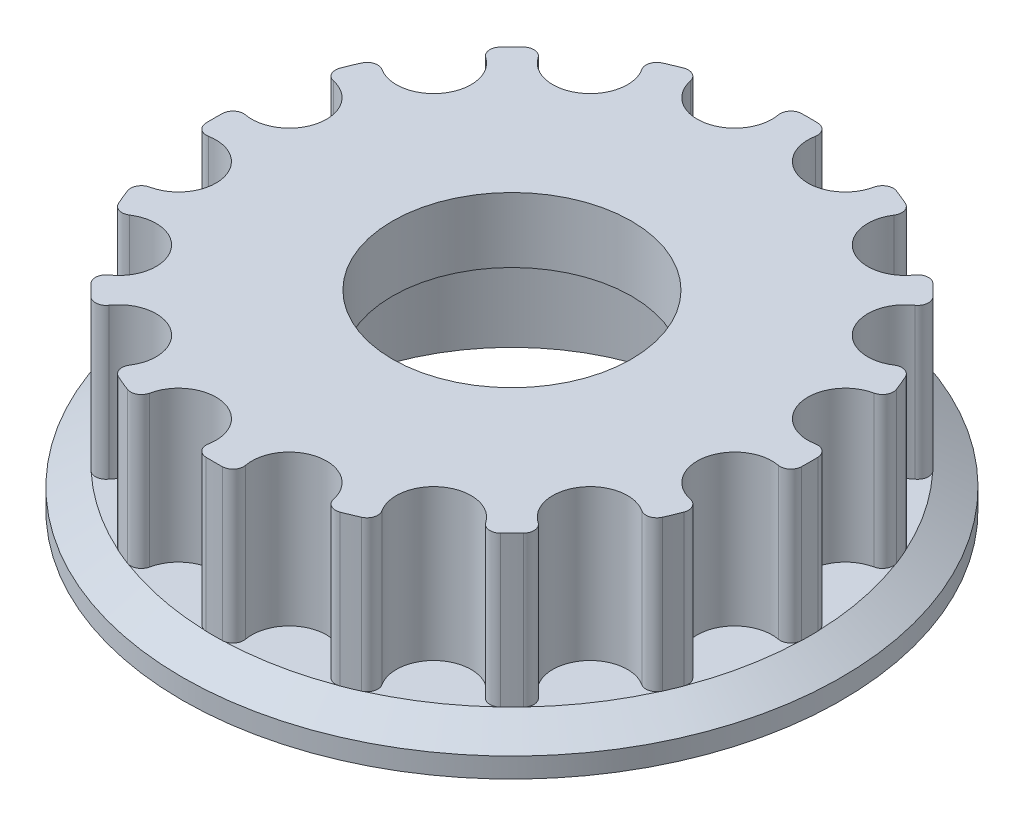
SolidWorks part; units mm, degrees
ref_plane "Front Plane" through (0, 0, 0) normal (0, 0, 1) x (1, 0, 0)
ref_plane "Top Plane" through (0, 0, 0) normal (0, 1, 0) x (1, 0, 0)
ref_plane "Right Plane" through (0, 0, 0) normal (1, 0, 0) x (0, 0, -1)
sketch "Sketch1" plane through (0, 0, 0) normal (0, 1, 0) x (1, 0, 0)
  circle A0 centre (0, 0) radius 12.7324
  dimension "D1" = 25.4648
extrude "Boss-Extrude1" add sketch "Sketch1" along normal blind 6
sketch "Sketch3" plane through (0, 0, 0) normal (0, 1, 0) x (1, 0, 0)
  line L3 (0, 0) -> (0, 11.8624) construction
  line L6 (0, 0) -> (2.484, 12.4877) construction
  line L8 (5.2552, 12.6871) -> (4.5395, 10.9594)
  line L9 (0, 13.7324) -> (0, 11.8624)
  arc A2 (0, 12.7324) -> (4.8725, 11.7632) centre (0, 0) cw construction
  arc A8 (0, 11.8624) -> (0.3276, 11.8579) centre (0, 0) cw
  arc A9 (0.7384, 11.3491) -> (0.3276, 11.8579) centre (0.3157, 11.428) ccw
  arc A12 (0.7384, 11.3491) -> (3.6609, 10.7677) centre (2.203, 11.0754) ccw
  arc A15 (3.6609, 10.7677) -> (4.2352, 11.0806) centre (4.0817, 10.6789) cw
  arc A16 (4.5395, 10.9594) -> (4.2352, 11.0806) centre (0, 0) ccw
  arc A17 (0, 13.7324) -> (5.2552, 12.6871) centre (0, 0) cw
  circle A18 centre (0, 0) radius 12.7324 construction
  dimension "D1" = 0.43
  dimension "D2" = 1.49
  dimension "D4" = 2.93
  dimension "D5" = 5
  dimension "D3" = 0.87
  dimension "D6" = 1
extrude "Cut-Extrude1" cut sketch "Sketch3" along normal up to surface (6 mm away) up to face at (0, 6, 12.7324)
pattern_circular "CirPattern1" count 16 over 360 about axis through (0, 6, 0) along (0, 1, 0) of "Cut-Extrude1"
sketch "Sketch5" plane through (0, 0, 0) normal (0, 0, 1) x (1, 0, 0)
  line L0 (0, 0) -> (0, -1.5875)
  line L1 (0, -1.5875) -> (-13.1279, -1.5875)
  line L2 (-13.1279, -1.5875) -> (-13.1279, -0.7938)
  line L3 (-13.1279, -0.7938) -> (-11.8579, 0)
  line L4 (55, 0) -> (-55, 0) construction
  line L5 (-11.8579, 0) -> (0, 0)
  line L6 (-11.8579, 6) -> (-11.8579, 0) construction
  dimension "D1" = 1.5875
  dimension "D2" = 0.7937
  dimension "D3" = 1.27
revolve "Revolve1" add sketch "Sketch5" angle 360 about axis through (0, 12.6943, 0) along (0, -1, 0)
sketch "Sketch4" plane through (0, -1.5875, 0) normal (0, -1, 0) x (1, 0, 0)
  circle A0 centre (0, 0) radius 7.9375
  circle A1 centre (0, 0) radius 4.7625
  dimension "D1" = 15.875
  dimension "D2" = 9.525
extrude "Cut-Extrude4" cut sketch "Sketch4" against normal blind 5 contours A0 A1 region at (-7.713, -1.5875, 0)
extrude "Cut-Extrude5" cut sketch "Sketch4<5>" against normal through all contours A1 region at (0, -1.5875, 0)
sketch "Sketch4<5>" plane through (0, -1.5875, 0) normal (0, -1, 0) x (1, 0, 0) same geometry as "Sketch4"
